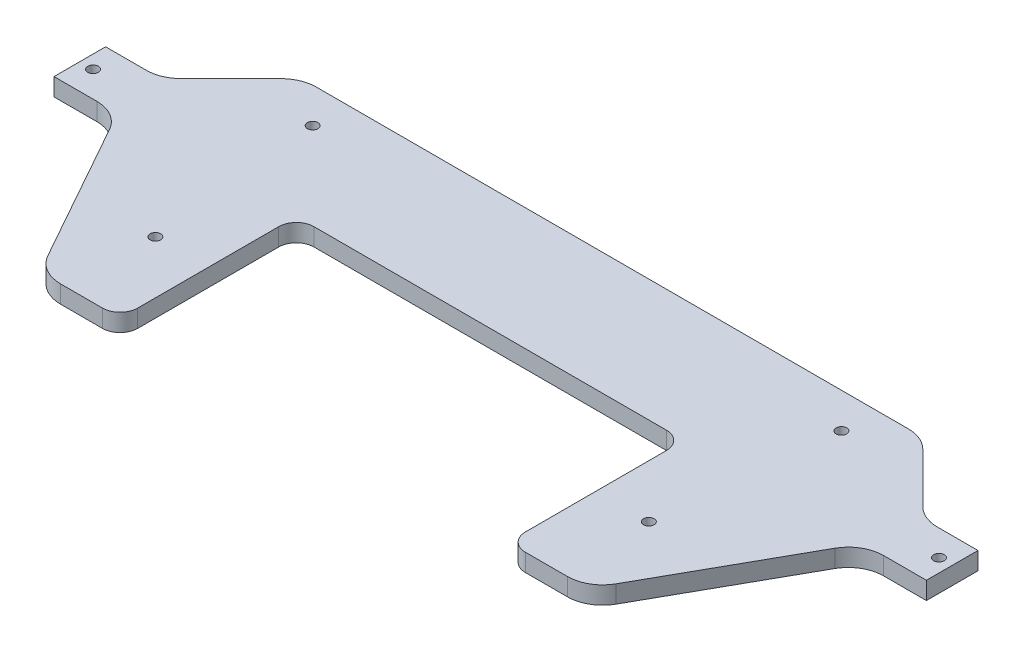
SolidWorks part; units mm, degrees
ref_plane "Alzado" through (0, 0, 0) normal (0, 0, 1) x (1, 0, 0)
ref_plane "Planta" through (0, 0, 0) normal (0, 1, 0) x (1, 0, 0)
ref_plane "Vista lateral" through (0, 0, 0) normal (1, 0, 0) x (0, 0, -1)
sketch "Croquis1" plane through (0, 0, 0) normal (0, 1, 0) x (1, 0, 0)
  line L0 (-27.8825, 0) -> (38.5584, 0) construction
  line L1 (-88.1, 42.3182) -> (88.1, 42.3182)
  line L2 (-77.75, -42.3182) -> (77.75, -42.3182)
  line L3 (-88.1, 42.3182) -> (-108.1, 22.3182)
  line L4 (-108.1, 22.3182) -> (-127.75, 22.3182)
  line L5 (0, 0) -> (0, 27.7067) construction
  line L6 (-127.75, 22.3182) -> (-127.75, 7.6818)
  line L7 (-127.75, 7.6818) -> (-105.75, 7.6818)
  line L8 (-105.75, 7.6818) -> (-77.75, -42.3182)
  line L9 (88.1, 42.3182) -> (108.1, 22.3182)
  line L10 (108.1, 22.3182) -> (127.75, 22.3182)
  line L11 (127.75, 22.3182) -> (127.75, 7.6818)
  line L12 (127.75, 7.6818) -> (105.75, 7.6818)
  line L13 (105.75, 7.6818) -> (77.75, -42.3182)
  dimension "D1" = 255.5
  dimension "D2" = 84.6363
  dimension "D3" = 19.65
  dimension "D4" = 22
  dimension "D5" = 22
  dimension "D6" = 50
  dimension "D7" = 50
  dimension "D8" = 50
  dimension "D9" = 20
  dimension "D10" = 20
extrude "Saliente-Extruir1" add sketch "Croquis1" along normal blind 5
fillet "Redondeo1" radius 10 8 edges at (88.1, 2.5, -42.3182) (-88.1, 2.5, -42.3182) (-77.75, 2.5, 42.3182) (77.75, 2.5, 42.3182) (108.1, 2.5, -22.3182) (105.75, 2.5, -7.6818) (-105.75, 2.5, -7.6818) (-108.1, 2.5, -22.3182)
sketch "Croquis2" plane through (0, 5, 0) normal (0, 1, 0) x (1, 0, 0)
  line L0 (0, 0) -> (0, -87.7887) construction
  line L1 (-119.9961, 22.3182) -> (-119.9961, 40.4374) construction
  line L2 (-112.2421, 22.3182) -> (-127.75, 22.3182) construction
  line L3 (-127.75, 15) -> (-123.2915, 15) construction
  line L4 (-127.75, 22.3182) -> (-127.75, 7.6818) construction
  line L5 (119.9961, 22.3182) -> (119.9961, 29.1715) construction
  line L6 (127.75, 22.3182) -> (112.2421, 22.3182) construction
  line L7 (115.6048, 15) -> (126.3231, 15) construction
  line L8 (83.9579, 42.3182) -> (-83.9579, 42.3182) construction
  line L10 (-71.8888, -42.3182) -> (71.8888, -42.3182) construction
  circle A0 centre (70, -17.3182) radius 1.5
  circle A1 centre (-70, -17.3182) radius 1.5
  circle A2 centre (-119.9961, 15) radius 1.5
  circle A3 centre (119.9961, 15) radius 1.5
  circle A4 centre (-75, 32.3182) radius 1.5
  circle A5 centre (75, 32.3182) radius 1.5
  circle A6 centre (-17.5, -17.3182) radius 1.5
  circle A7 centre (17.5, -17.3182) radius 1.5
  circle A8 centre (-17.5, -37.3182) radius 1.5
  circle A9 centre (17.5, -37.3182) radius 1.5
  dimension "D1" = 3
  dimension "D2" = 3
  dimension "D7" = 3
  dimension "D8" = 3
  dimension "D10" = 3
  dimension "D11" = 3
  dimension "D17" = 3
  dimension "D18" = 3
  dimension "D19" = 3
  dimension "D20" = 3
  dimension "D3" = 75
  dimension "D4" = 75
  dimension "D5" = 10
  dimension "D6" = 10
  dimension "D9" = 140
  dimension "D12" = 25
  dimension "D13" = 35
  dimension "D14" = 35
  dimension "D15" = 5
  dimension "D16" = 20
extrude "Cortar-Extruir1" cut sketch "Croquis2" against normal through all
sketch "Croquis4" plane through (0, 5, 0) normal (0, 1, 0) x (1, 0, 0)
  line L0 (-55, -42.3182) -> (-55, 7.6818)
  line L1 (-55, 7.6818) -> (55, 7.6818)
  line L2 (55, 7.6818) -> (55, -42.3182)
  line L3 (55, -42.3182) -> (-55, -42.3182)
  line L4 (0, 0) -> (0, 21.6247) construction
  line L5 (-71.8888, -42.3182) -> (71.8888, -42.3182) construction
  dimension "D1" = 110
  dimension "D2" = 50
extrude "Cortar-Extruir2" cut sketch "Croquis4" against normal through all
fillet "Redondeo2" radius 5 4 edges at (-55, 2.5, 42.3182) (55, 2.5, 42.3182) (55, 2.5, -7.6818) (-55, 2.5, -7.6818)
sketch "Croquis5" plane through (0, 5, 0) normal (0, 1, 0) x (1, 0, 0)
  line L0 (-127.75, 22.3182) -> (-127.75, 7.6818)
  line L1 (-127.75, 7.6818) -> (-123.75, 7.6818)
  line L2 (-127.75, 7.6818) -> (-111.6112, 7.6818) construction
  line L3 (-123.75, 7.6818) -> (-123.75, 22.3182)
  line L4 (-112.2421, 22.3182) -> (-127.75, 22.3182) construction
  line L5 (-123.75, 22.3182) -> (-127.75, 22.3182)
  line L6 (127.75, 22.3182) -> (127.75, 7.6818)
  line L7 (127.75, 7.6818) -> (123.75, 7.6818)
  line L8 (111.6112, 7.6818) -> (127.75, 7.6818) construction
  line L9 (123.75, 7.6818) -> (123.75, 22.3182)
  line L10 (127.75, 22.3182) -> (112.2421, 22.3182) construction
  line L11 (123.75, 22.3182) -> (127.75, 22.3182)
  dimension "D1" = 4
  dimension "D2" = 4
extrude "Cortar-Extruir3" cut sketch "Croquis5" against normal through all
